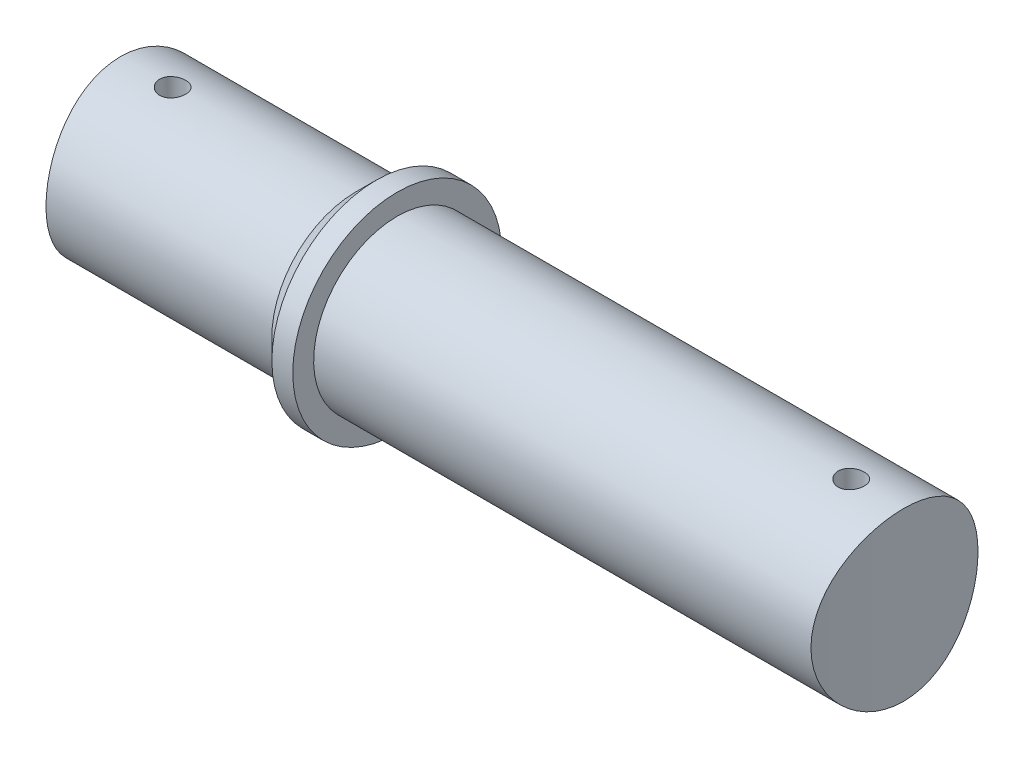
SolidWorks part; units mm, degrees
ref_plane "Front Plane" through (0, 0, 0) normal (0, 0, 1) x (1, 0, 0)
ref_plane "Top Plane" through (0, 0, 0) normal (0, 1, 0) x (1, 0, 0)
ref_plane "Right Plane" through (0, 0, 0) normal (1, 0, 0) x (0, 0, -1)
sketch "Sketch1" plane through (0, 0, 0) normal (0, 0, 1) x (1, 0, 0)
  line L0 (0, 0) -> (-22.5779, 0) construction
  line L1 (-18.75, 0) -> (18.75, 0)
  line L2 (-18.75, 0) -> (-18.75, 4)
  line L3 (18.75, 0) -> (18.75, 4)
  line L4 (-18.75, 4) -> (18.75, 4)
  line L5 (-0.625, 0.625) -> (-0.625, 0)
  line L6 (-16.875, 0.625) -> (16.875, 0.625)
  line L7 (16.875, 0.625) -> (16.875, 0)
  line L8 (16.875, 0) -> (16.875, -0.625)
  line L9 (16.875, -0.625) -> (16.25, -0.625)
  line L10 (15.625, -0.625) -> (15.625, 4) construction
  line L11 (16.875, 0.625) -> (16.875, 4)
  line L12 (16.25, -0.625) -> (16.25, 4)
  line L13 (16.25, -0.625) -> (15.625, -0.625) construction
  line L14 (0, 0) -> (0, 4) construction
  line L15 (-16.875, 0.625) -> (-16.875, 0)
  line L16 (-16.875, 0.625) -> (-16.875, 4) construction
  line L17 (-16.875, 0) -> (-16.875, -0.625) construction
  line L18 (-16.875, -0.625) -> (-16.25, -0.625) construction
  line L19 (-16.25, -0.625) -> (-16.25, 4) construction
  line L20 (-16.25, -0.625) -> (-15.625, -0.625) construction
  line L21 (-15.625, -0.625) -> (-15.625, 4) construction
  line L22 (-0.625, 0) -> (-0.625, -4)
  line L23 (-0.625, -4) -> (0, -4)
  line L24 (0, -4) -> (0, 0)
  line L25 (0, -4) -> (0.625, -4) construction
  line L26 (0.625, -4) -> (0.625, 0) construction
  line L27 (0, 0.625) -> (0, 0)
  line L28 (16.25, -0.625) -> (16.25, -3.4097) construction
  point P1 (0, 0)
  dimension "D1" = 37.5
  dimension "D2" = 4
  dimension "D3" = 2.5
  dimension "D4" = 2.5
revolve "Revolve1" add sketch "Sketch1" angle 360 about L0 region at (-1.4127, 2.2929, 0) region at (16.5625, 2.3125, 0) region at (17.8125, 2, 0)
revolve "Cut-Revolve1" cut sketch "Sketch1<3>" angle 360 about L14 region at (-0.3125, 0.3125, 0) region at (-0.3125, -2, 0)
sketch "Sketch1<3>" plane through (0, 0, 0) normal (0, 0, 1) x (1, 0, 0) same geometry as "Sketch1"
revolve "Cut-Revolve2" cut sketch "Sketch1<4>" angle 360 about L28 region at (16.5625, 2.3125, 0) region at (16.5625, 0.3125, 0) region at (16.5625, -0.3125, 0)
sketch "Sketch1<4>" plane through (0, 0, 0) normal (0, 0, 1) x (1, 0, 0) same geometry as "Sketch1"
mirror "Mirror1" about plane through (0, 0, 0) normal (1, 0, 0) of "Cut-Revolve2"
sketch "Sketch2" plane through (0, 0, 0) normal (0, 1, 0) x (1, 0, 0)
  line L0 (18.75, -4) -> (18.75, 4) construction
  line L1 (-18.75, 4) -> (-18.75, -4) construction
  line L2 (-18.75, 4) -> (-18.75, -4)
  line L3 (18.75, -4) -> (18.75, 4)
  line L4 (18.75, 4) -> (-18.75, 4) construction
  line L5 (-18.75, -4) -> (18.75, -4) construction
  line L6 (18.75, 4) -> (18.3184, 4)
  line L7 (-18.75, -4) -> (-18.3184, -4)
  line L8 (-18.3184, 4) -> (-18.75, 4)
  line L9 (18.3184, -4) -> (18.75, -4)
  arc A0 (18.3184, -4) -> (18.3184, 4) centre (0, 0) ccw
  arc A1 (-18.3184, 4) -> (-18.3184, -4) centre (0, 0) ccw
extrude "Cut-Extrude1" cut sketch "Sketch2" against normal through all both and the other way through all contours A1 L2 L7 | A1 L8 L2 | A0 L9 L3 | A0 L3 L6 region at (-18.6208, 0, -3.0023) region at (-18.6208, 0, 3.0023) region at (18.6208, 0, 3.0023) region at (18.6208, 0, -3.0023)
sketch "Sketch3" plane through (0, 0, 0) normal (0, 0, 1) x (1, 0, 0)
  line L0 (-5.5, 4) -> (-5.5, 5)
  line L1 (15.625, 4) -> (-15.6251, 4) construction
  line L2 (-5.5, 5) -> (-6.5, 5)
  line L3 (-6.5, 5) -> (-7.5, 4)
  line L4 (-5.5, 4) -> (-7.5, 4)
  dimension "D1" = 45
  dimension "D2" = 1
  dimension "D3" = 5.5
revolve "Revolve2" add sketch "Sketch3" angle 360 about L0
sketch "Sketch4" plane through (0, 0, 0) normal (1, 0, 0) x (0, 0, -1)
  circle A1 centre (0, 0) radius 4
  point P1 (-0.1504, -0.4435)
  point P3 (0, 0)
